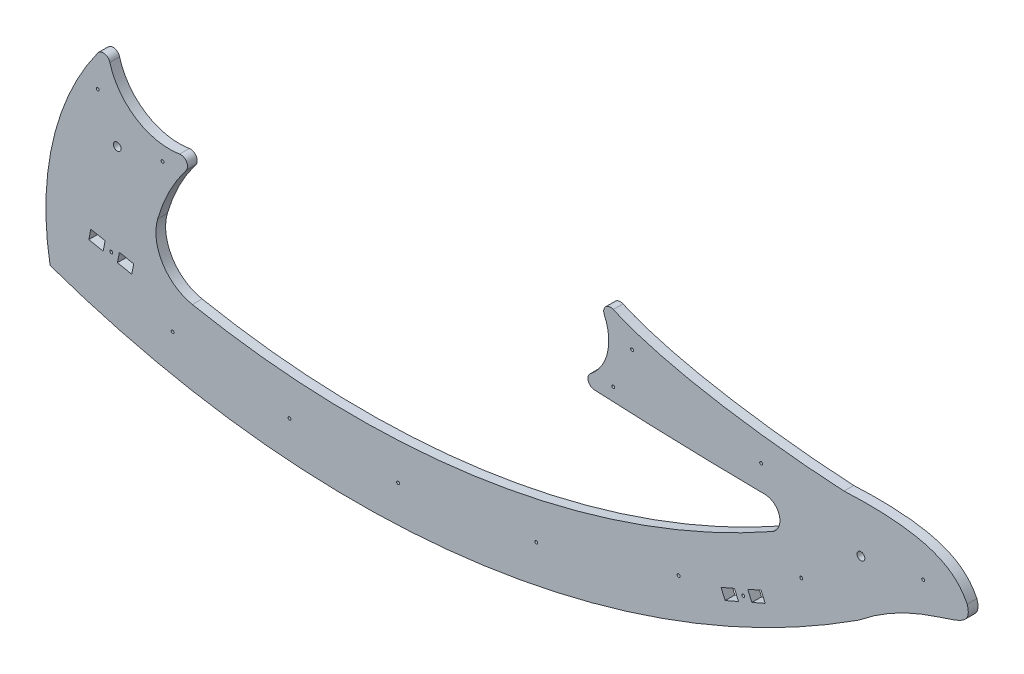
SolidWorks part; units mm, degrees
material "Teak"
ref_plane "Front Plane" through (0, 0, 0) normal (0, 0, 1) x (1, 0, 0)
ref_plane "Top Plane" through (0, 0, 0) normal (0, 1, 0) x (1, 0, 0)
ref_plane "Right Plane" through (0, 0, 0) normal (1, 0, 0) x (0, 0, -1)
sketch "Несущая боковая" plane through (0, 0, 0) normal (0, 0, 1) x (1, 0, 0)
  line L6 (398.785, -200.6515) -> (-79.2948, -202.7)
  arc A0 (568.0858, 187.1743) -> (604.9253, 231.748) centre (555.0835, 235.431) ccw
  arc A1 (604.9253, 231.748) -> (587.3016, 257.9076) centre (579.4885, 233.6276) ccw
  arc A2 (587.3016, 257.9076) -> (556.344, 256.9224) centre (573.2016, 214.0906) ccw
  arc A4 (-130.7033, -495.9282) -> (-177.7889, -420.4808) centre (-169.1009, -467.4752) ccw
  arc A7 (-130.7033, -495.9282) -> (-181.6944, -712.4375) centre (95.3308, -663.4217) ccw
  arc A8 (-183.8786, -325.353) -> (-177.7889, -420.4808) centre (-186.515, -373.2806) ccw
  arc A9 (-112.9747, -345.6094) -> (-183.8786, -325.353) centre (-193.0224, -491.581) ccw
  arc A11 (23.5507, -511.1423) -> (553.7515, -548.6326) centre (601.0308, 3887.8918) ccw
  arc A12 (7.2112, -514.4863) -> (-70.9864, -615.6156) centre (95.3308, -663.4217) ccw
  arc A13 (-70.9864, -615.6156) -> (-35.2447, -674.0637) centre (-26.3207, -628.4543) ccw
  arc A14 (23.5507, -511.1423) -> (7.2112, -514.4863) centre (20.2245, -536.4807) ccw
  arc A15 (-181.6944, -712.4375) -> (650.1904, -612.5982) centre (132.6498, 184.0228) ccw
  arc A16 (-35.2447, -674.0637) -> (561.2917, -578.0579) centre (132.6498, 184.0228) ccw
  arc A17 (561.2917, -578.0579) -> (553.7515, -548.6326) centre (553.584, -564.3543) ccw
  spline S0 degree 3 poles (556.344, 256.9224) (413.4931, 200.7) (492.8039, -30.4464) (410.7267, -175.5993) knots 0.000401 0.000401 0.000401 0.000401 0.043478 0.043478 0.043478 0.043478
  spline S1 degree 3 poles (410.7267, -175.5993) (407.231, -184.6492) (403.2193, -192.9282) (398.785, -200.6515) knots 0.043478 0.043478 0.043478 0.043478 0.086957 0.086957 0.086957 0.086957
  spline S2 degree 3 poles (-79.2948, -202.7) (-78.5172, -227.7) (-66.7741, -249.7094) (-44.1772, -268.7587) knots 0.130435 0.130435 0.130435 0.130435 0.173913 0.173913 0.173913 0.173913
  spline S3 degree 3 poles (-44.1772, -268.7587) (-12.7058, -245.829) (38.9597, -231.7344) (82.6666, -241.804) knots 0.173913 0.173913 0.173913 0.173913 0.217391 0.217391 0.217391 0.217391
  spline S4 degree 3 poles (82.6666, -241.804) (105.6787, -251.6525) (111.2464, -268.6919) (94.2115, -290.7234) knots 0.217391 0.217391 0.217391 0.217391 0.26087 0.26087 0.26087 0.26087
  spline S5 degree 3 poles (94.2115, -290.7234) (87.1581, -299.8457) (74.9831, -308.4217) (61.0599, -320.5021) knots 0.26087 0.26087 0.26087 0.26087 0.304348 0.304348 0.304348 0.304348
  spline S6 degree 3 poles (61.0599, -320.5021) (47.3806, -331.8412) (34.8832, -345.2678) (22.8705, -359.1067) knots 0.304348 0.304348 0.304348 0.304348 0.347826 0.347826 0.347826 0.347826
  spline S7 degree 3 poles (22.8705, -359.1067) (-5.5844, -391.8897) (-25.5922, -386.6363) (-46.4172, -376.7876) knots 0.347826 0.347826 0.347826 0.347826 0.391304 0.391304 0.391304 0.391304
  spline S8 degree 3 poles (-46.4172, -376.7876) (-71.9902, -366.2219) (-92.784, -356.6815) (-112.9747, -345.6094) knots 0.391304 0.391304 0.391304 0.391304 0.434783 0.434783 0.434783 0.434783
  spline S15 degree 3 poles (650.1904, -612.5982) (721.7263, -555.1366) (771.3742, -572.8028) (761.971, -542.4383) knots 0.695652 0.695652 0.695652 0.695652 0.73913 0.73913 0.73913 0.73913
  spline S16 degree 3 poles (761.971, -542.4383) (749.9881, -518.2511) (723.1034, -500.8362) (635.2399, -505.0064) knots 0.73913 0.73913 0.73913 0.73913 0.782609 0.782609 0.782609 0.782609
  spline S17 degree 3 poles (635.2399, -505.0064) (572.992, -501.9328) (433.5503, -486.7788) (380.9104, -452.9037) knots 0.782609 0.782609 0.782609 0.782609 0.826087 0.826087 0.826087 0.826087
  spline S18 degree 3 poles (380.9104, -452.9037) (364.7659, -442.5143) (356.7862, -430.3638) (361.7026, -416.2609) knots 0.826087 0.826087 0.826087 0.826087 0.869565 0.869565 0.869565 0.869565
  spline S19 degree 3 poles (361.7026, -416.2609) (369.7577, -319.5618) (455.7474, -287.137) (480.2427, -200.3025) knots 0.869565 0.869565 0.869565 0.869565 0.913043 0.913043 0.913043 0.913043
  spline S20 degree 3 poles (480.2427, -200.3025) (553.5443, -5.6015) (495.01, 115.2768) (568.0858, 187.1743) knots 0.913043 0.913043 0.913043 0.913043 0.956522 0.956522 0.956522 0.956522
  spline S31 degree 3 poles (97.4618, -368.9486) (168.6207, -296.3511) (255.442, -250.0892) (374.5085, -234.3308) knots 0.75 0.75 0.75 0.75 1 1 1 1
  spline S32 degree 3 poles (92.0908, -427.5464) (69.7947, -412.5311) (70.4905, -396.4567) (97.4618, -368.9486) knots 0.5 0.5 0.5 0.5 0.75 0.75 0.75 0.75
  spline S33 degree 3 poles (247.8827, -396.6458) (222.4754, -441.0979) (152.6914, -451.7196) (92.0908, -427.5464) knots 0.25 0.25 0.25 0.25 0.5 0.5 0.5 0.5
  spline S34 degree 3 poles (374.5085, -234.3308) (336.7044, -278.0035) (285.6362, -310.9643) (247.8827, -396.6458) knots 0 0 0 0 0.25 0.25 0.25 0.25
  dimension "D2" = 48
sketch "Боковая под поперечины" plane through (0, 0, 0) normal (0, 0, 1) x (1, 0, 0)
  line L15 (-159.6049, -346.9107) -> (-207.6507, -344.8161) construction
  line L16 (-207.6507, -344.8161) -> (-218.5759, -409.003)
  line L56 (-207.6507, -344.8161) -> (-159.6963, -346.9068)
  line L57 (-159.6963, -346.9068) -> (-148.2015, -350.3521)
  line L58 (-148.2015, -350.3521) -> (-104.2437, -369.6319)
  line L59 (-104.2437, -369.6319) -> (-95.353, -374.2095)
  line L60 (-95.353, -374.2095) -> (-51.5894, -393.9261)
  line L61 (-51.5894, -393.9261) -> (-42.3459, -397.7417)
  line L62 (-42.3459, -397.7417) -> (2.1537, -415.7357)
  line L63 (2.1537, -415.7357) -> (11.4455, -419.432)
  line L64 (11.4455, -419.432) -> (56.3986, -436.2612)
  line L65 (56.3986, -436.2612) -> (65.8381, -439.5619)
  line L66 (65.8381, -439.5619) -> (111.7403, -453.5971)
  line L67 (111.7403, -453.5971) -> (121.3499, -456.3643)
  line L68 (121.3499, -456.3643) -> (169.2689, -459.1514)
  line L69 (169.2689, -459.1514) -> (179.2066, -458.0374)
  line L70 (179.2066, -458.0374) -> (224.5179, -442.198)
  line L71 (224.5179, -442.198) -> (232.8956, -436.7378)
  line L72 (232.8956, -436.7378) -> (261.7321, -398.3651)
  line L73 (261.7321, -398.3651) -> (267.2053, -389.9959)
  line L74 (267.2053, -389.9959) -> (294.9373, -350.8177)
  line L75 (294.9373, -350.8177) -> (300.8954, -342.7864)
  line L76 (300.8954, -342.7864) -> (330.585, -305.0699)
  line L77 (330.585, -305.0699) -> (336.9867, -297.3877)
  line L78 (336.9867, -297.3877) -> (368.9263, -261.5566)
  line L79 (368.9263, -261.5566) -> (376.1332, -254.6241)
  line L80 (376.1332, -254.6241) -> (406.9239, -217.801)
  line L81 (406.9239, -217.801) -> (412.4436, -209.4624)
  line L82 (412.4436, -209.4624) -> (434.4129, -166.7851)
  line L83 (438.0837, -157.4832) -> (452.6073, -111.7332)
  line L84 (452.6073, -111.7332) -> (454.9033, -102.0003)
  line L85 (454.9033, -102.0003) -> (464.25, -54.9191)
  line L86 (464.25, -54.9191) -> (465.6878, -45.023)
  line L87 (465.6878, -45.023) -> (472.014, 2.5582)
  line L88 (472.014, 2.5582) -> (473.0512, 12.5043)
  line L89 (473.0512, 12.5043) -> (478.3742, 60.2082)
  line L90 (478.3742, 60.2082) -> (479.4656, 70.1485)
  line L91 (479.4656, 70.1485) -> (486.2184, 117.6711)
  line L92 (486.2184, 117.6711) -> (487.9962, 127.5118)
  line L93 (487.9962, 127.5118) -> (500.2801, 173.9134)
  line L94 (500.2801, 173.9134) -> (504.8877, 188.1882)
  line L95 (504.8877, 188.1882) -> (532.6089, 227.3741)
  line L96 (532.6089, 227.3741) -> (546.1164, 235.9502)
  line L97 (546.1164, 235.9502) -> (589.1375, 257.2382)
  line L99 (434.4129, -166.7851) -> (438.0837, -157.4832)
  arc A4 (568.0858, 187.1743) -> (604.9253, 231.748) centre (554.9668, 235.5274) ccw
  arc A7 (604.9253, 231.748) -> (589.1375, 257.2382) centre (579.4223, 233.5866) ccw
  arc A10 (604.9253, 231.748) -> (587.3016, 257.9076) centre (579.4885, 233.6276) ccw construction
  arc A11 (-121.8206, -474.4411) -> (-17.3364, -532.0713) centre (-58.8058, -483.7252) ccw
  arc A12 (7.2112, -514.4863) -> (-17.3364, -532.0713) centre (95.3308, -663.4217) ccw
  arc A13 (23.5507, -511.1423) -> (7.2112, -514.4863) centre (20.2245, -536.4807) ccw
  arc A15 (-121.8206, -474.4411) -> (-177.7889, -420.4808) centre (-169.1009, -467.4752) ccw
  arc A16 (23.5507, -511.1423) -> (341.0431, -541.2606) centre (601.0308, 3887.8918) ccw
  arc A17 (-130.7033, -495.9282) -> (-177.7889, -420.4808) centre (-169.1009, -467.4752) ccw construction
  arc A18 (-183.8786, -325.353) -> (-177.7889, -420.4808) centre (-186.515, -373.2806) ccw construction
  arc A19 (-218.5759, -409.003) -> (-177.7889, -420.4808) centre (-186.515, -373.2806) ccw
  arc A20 (23.5507, -511.1423) -> (553.7515, -548.6326) centre (601.0308, 3887.8918) ccw construction
  arc A21 (23.5507, -511.1423) -> (7.2112, -514.4863) centre (20.2245, -536.4807) ccw construction
  arc A22 (7.2112, -514.4863) -> (-70.9864, -615.6156) centre (95.3308, -663.4217) ccw construction
  arc A23 (341.0431, -541.2606) -> (375.7523, -454.4299) centre (343.931, -492.0624) ccw
  spline S13 degree 3 poles (375.7523, -454.4299) (361.34, -442.2431) (355.1113, -429.3811) (361.7026, -416.2609) knots 0.5 0.5 0.5 0.5 0.533333 0.533333 0.533333 0.533333
  spline S14 degree 3 poles (361.7026, -416.2609) (369.7577, -319.5618) (455.7474, -287.137) (480.2427, -200.3025) knots 0.533333 0.533333 0.533333 0.533333 0.566667 0.566667 0.566667 0.566667
  spline S15 degree 3 poles (480.2427, -200.3025) (553.5444, -5.6014) (495.0101, 115.2768) (568.0858, 187.1743) knots 0.566667 0.566667 0.566667 0.566667 0.6 0.6 0.6 0.6
  point P66 (608.2751, 264.1653)
  point P67 (553.7309, 240.2756)
  point P74 (-221.3236, -344.22)
  dimension "D1" = 48
  dimension "D2" = 12
  dimension "D3" = 10
  dimension "D10" = 16
  dimension "D11" = 15
extrude "Несущая" add sketch "Несущая боковая" along normal blind 10
extrude "Боковая" [suppressed] add sketch "Боковая под поперечины" along normal blind 10
sketch "Sketch3" [suppressed] plane through (0, 0, 0) normal (0, 0, 1) x (1, 0, 0)
  line L0 (546.1164, 235.9502) -> (589.1375, 257.2382) construction
  line L2 (-206.3501, -396.7709) -> (-202.6586, -375.0829)
  line L3 (-216.2083, -395.093) -> (-212.5168, -373.4049)
  line L6 (-216.2083, -395.093) -> (-206.3501, -396.7709)
  line L10 (-207.6507, -344.8161) -> (-194.6631, -345.3823) construction
  line L11 (-207.6507, -344.8161) -> (-208.0863, -354.8066) construction
  line L12 (-159.6963, -346.9068) -> (-160.1319, -356.8973) construction
  line L13 (-208.0863, -354.8066) -> (-195.0986, -355.3728) construction
  line L14 (-194.6631, -345.3823) -> (-195.0986, -355.3728)
  line L15 (-172.684, -346.3405) -> (-173.1195, -356.331)
  line L16 (-173.1195, -356.331) -> (-160.1319, -356.8973) construction
  line L17 (-195.0986, -355.3728) -> (-173.1195, -356.331)
  line L18 (-172.684, -346.3405) -> (-159.6963, -346.9068) construction
  line L19 (-194.6631, -345.3823) -> (-172.684, -346.3405)
  line L37 (-136.2963, -355.5737) -> (-140.3129, -364.7316)
  line L38 (-116.149, -364.4103) -> (-120.1656, -373.5681)
  line L40 (-152.2182, -359.51) -> (-140.3129, -364.7316) construction
  line L41 (-116.149, -364.4103) -> (-104.2437, -369.6319) construction
  line L42 (-140.3129, -364.7316) -> (-120.1656, -373.5681)
  line L43 (-104.2437, -369.6319) -> (-108.2603, -378.7897) construction
  line L44 (-120.1656, -373.5681) -> (-108.2603, -378.7897) construction
  line L45 (-148.2015, -350.3521) -> (-136.2963, -355.5737) construction
  line L46 (-136.2963, -355.5737) -> (-116.149, -364.4103)
  line L47 (-148.2015, -350.3521) -> (-152.2182, -359.51) construction
  line L48 (-104.2437, -369.6319) -> (-148.2015, -350.3521) construction
  line L49 (-63.442, -388.5862) -> (-67.5496, -397.7036)
  line L50 (-83.5003, -379.5494) -> (-63.442, -388.5862)
  line L51 (-83.5003, -379.5494) -> (-87.608, -388.6668)
  line L52 (-63.442, -388.5862) -> (-51.5894, -393.9261) construction
  line L53 (-99.4606, -383.3269) -> (-87.608, -388.6668) construction
  line L54 (-51.5894, -393.9261) -> (-55.697, -403.0436) construction
  line L55 (-95.353, -374.2095) -> (-83.5003, -379.5494) construction
  line L56 (-87.608, -388.6668) -> (-67.5496, -397.7036)
  line L57 (-67.5496, -397.7036) -> (-55.697, -403.0436) construction
  line L58 (-95.353, -374.2095) -> (-99.4606, -383.3269) construction
  line L59 (-34.0427, -411.8858) -> (-13.647, -420.1331)
  line L60 (-30.2939, -402.615) -> (-9.8983, -410.8623)
  line L61 (-42.3459, -397.7417) -> (-30.2939, -402.615) construction
  line L62 (-9.8983, -410.8623) -> (2.1537, -415.7357) construction
  line L63 (-46.0946, -407.0124) -> (-34.0427, -411.8858) construction
  line L64 (-9.8983, -410.8623) -> (-13.647, -420.1331)
  line L65 (-42.3459, -397.7417) -> (-46.0946, -407.0124) construction
  line L66 (-13.647, -420.1331) -> (-1.595, -425.0064) construction
  line L67 (-30.2939, -402.615) -> (-34.0427, -411.8858)
  line L68 (2.1537, -415.7357) -> (-1.595, -425.0064) construction
  line L69 (44.2238, -431.7033) -> (40.7177, -441.0685)
  line L70 (56.3986, -436.2612) -> (52.8925, -445.6264) construction
  line L71 (23.6203, -423.9899) -> (44.2238, -431.7033)
  line L72 (23.6203, -423.9899) -> (20.1142, -433.3551)
  line L73 (7.9394, -428.7972) -> (20.1142, -433.3551) construction
  line L74 (11.4455, -419.432) -> (23.6203, -423.9899) construction
  line L75 (44.2238, -431.7033) -> (56.3986, -436.2612) construction
  line L76 (11.4455, -419.432) -> (7.9394, -428.7972) construction
  line L77 (40.7177, -441.0685) -> (52.8925, -445.6264) construction
  line L78 (20.1142, -433.3551) -> (40.7177, -441.0685)
  line L79 (96.3845, -459.3589) -> (108.8163, -463.1601) construction
  line L80 (65.8381, -439.5619) -> (62.9141, -449.1249) construction
  line L81 (99.3085, -449.7959) -> (96.3845, -459.3589)
  line L82 (78.27, -443.3631) -> (75.346, -452.9261)
  line L83 (65.8381, -439.5619) -> (78.27, -443.3631) construction
  line L84 (62.9141, -449.1249) -> (75.346, -452.9261) construction
  line L85 (99.3085, -449.7959) -> (111.7403, -453.5971) construction
  line L86 (111.7403, -453.5971) -> (108.8163, -463.1601) construction
  line L87 (75.346, -452.9261) -> (96.3845, -459.3589)
  line L88 (78.27, -443.3631) -> (99.3085, -449.7959)
  line L89 (120.7692, -466.3474) -> (133.7473, -467.1023) construction
  line L90 (156.2908, -458.3965) -> (169.2689, -459.1514) construction
  line L91 (133.7473, -467.1023) -> (155.7102, -468.3797)
  line L92 (156.2908, -458.3965) -> (155.7102, -468.3797)
  line L93 (155.7102, -468.3797) -> (168.6882, -469.1345) construction
  line L94 (121.3499, -456.3643) -> (134.3279, -457.1191) construction
  line L95 (134.3279, -457.1191) -> (156.2908, -458.3965)
  line L96 (121.3499, -456.3643) -> (120.7692, -466.3474) construction
  line L97 (134.3279, -457.1191) -> (133.7473, -467.1023)
  line L98 (169.2689, -459.1514) -> (168.6882, -469.1345) construction
  line L99 (215.546, -455.9277) -> (227.8178, -451.6378) construction
  line L100 (191.4784, -453.7475) -> (212.2461, -446.4878)
  line L101 (191.4784, -453.7475) -> (194.7783, -463.1874)
  line L102 (182.5065, -467.4772) -> (194.7783, -463.1874) construction
  line L103 (224.5179, -442.198) -> (227.8178, -451.6378) construction
  line L104 (194.7783, -463.1874) -> (215.546, -455.9277)
  line L105 (179.2066, -458.0374) -> (182.5065, -467.4772) construction
  line L106 (212.2461, -446.4878) -> (224.5179, -442.198) construction
  line L107 (179.2066, -458.0374) -> (191.4784, -453.7475) construction
  line L108 (212.2461, -446.4878) -> (215.546, -455.9277)
  line L109 (248.6998, -432.3528) -> (261.9165, -414.7653)
  line L110 (261.9165, -414.7653) -> (269.7264, -404.3728) construction
  line L111 (240.8899, -442.7454) -> (248.6998, -432.3528) construction
  line L112 (240.7055, -426.3452) -> (248.6998, -432.3528)
  line L113 (253.9222, -408.7577) -> (261.7321, -398.3651) construction
  line L114 (261.7321, -398.3651) -> (269.7264, -404.3728) construction
  line L115 (232.8956, -436.7378) -> (240.7055, -426.3452) construction
  line L116 (240.7055, -426.3452) -> (253.9222, -408.7577)
  line L117 (232.8956, -436.7378) -> (240.8899, -442.7454) construction
  line L118 (253.9222, -408.7577) -> (261.9165, -414.7653)
  line L119 (267.2053, -389.9959) -> (274.7161, -379.3851) construction
  line L120 (267.2053, -389.9959) -> (275.3674, -395.7734) construction
  line L121 (275.3674, -395.7734) -> (282.8782, -385.1626) construction
  line L122 (274.7161, -379.3851) -> (282.8782, -385.1626)
  line L123 (282.8782, -385.1626) -> (295.5887, -367.2059)
  line L124 (287.4266, -361.4284) -> (295.5887, -367.2059)
  line L125 (294.9373, -350.8177) -> (303.0995, -356.5952) construction
  line L126 (295.5887, -367.2059) -> (303.0995, -356.5952) construction
  line L127 (287.4266, -361.4284) -> (294.9373, -350.8177) construction
  line L128 (274.7161, -379.3851) -> (287.4266, -361.4284)
  line L129 (330.4016, -321.4701) -> (338.4426, -311.2553) construction
  line L130 (316.7939, -338.7569) -> (330.4016, -321.4701)
  line L131 (308.9363, -332.5715) -> (322.5441, -315.2848)
  line L132 (300.8954, -342.7864) -> (308.9363, -332.5715) construction
  line L133 (300.8954, -342.7864) -> (308.753, -348.9717) construction
  line L134 (308.9363, -332.5715) -> (316.7939, -338.7569)
  line L135 (322.5441, -315.2848) -> (330.4016, -321.4701)
  line L136 (308.753, -348.9717) -> (316.7939, -338.7569) construction
  line L137 (330.585, -305.0699) -> (338.4426, -311.2553) construction
  line L138 (322.5441, -315.2848) -> (330.585, -305.0699) construction
  line L139 (336.9867, -297.3877) -> (344.4515, -304.0418) construction
  line L140 (360.276, -271.2609) -> (367.7408, -277.915)
  line L141 (367.7408, -277.915) -> (376.3911, -268.2107) construction
  line L142 (344.4515, -304.0418) -> (353.1018, -294.3375) construction
  line L143 (353.1018, -294.3375) -> (367.7408, -277.915)
  line L144 (336.9867, -297.3877) -> (345.637, -287.6834) construction
  line L145 (368.9263, -261.5566) -> (376.3911, -268.2107) construction
  line L146 (360.276, -271.2609) -> (368.9263, -261.5566) construction
  line L147 (345.637, -287.6834) -> (360.276, -271.2609)
  line L148 (345.637, -287.6834) -> (353.1018, -294.3375)
  line L149 (406.2562, -234.1886) -> (414.5953, -224.2157) construction
  line L150 (398.5847, -227.7739) -> (406.2562, -234.1886)
  line L151 (392.1438, -251.0659) -> (406.2562, -234.1886)
  line L152 (383.8047, -261.0388) -> (392.1438, -251.0659) construction
  line L153 (406.9239, -217.801) -> (414.5953, -224.2157) construction
  line L154 (376.1332, -254.6241) -> (384.4724, -244.6512) construction
  line L155 (376.1332, -254.6241) -> (383.8047, -261.0388) construction
  line L156 (398.5847, -227.7739) -> (406.9239, -217.801) construction
  line L157 (384.4724, -244.6512) -> (392.1438, -251.0659)
  line L158 (384.4724, -244.6512) -> (398.5847, -227.7739)
  line L159 (437.354, -182.9205) -> (443.304, -171.3621) construction
  line L160 (428.4629, -178.3436) -> (434.4129, -166.7851) construction
  line L161 (428.4629, -178.3436) -> (437.354, -182.9205)
  line L162 (418.3936, -197.904) -> (427.2847, -202.4809)
  line L163 (427.2847, -202.4809) -> (437.354, -182.9205)
  line L164 (412.4436, -209.4624) -> (421.3346, -214.0393) construction
  line L165 (421.3346, -214.0393) -> (427.2847, -202.4809) construction
  line L166 (434.4129, -166.7851) -> (443.304, -171.3621) construction
  line L167 (418.3936, -197.904) -> (428.4629, -178.3436)
  line L168 (412.4436, -209.4624) -> (418.3936, -197.904) construction
  line L169 (447.6149, -160.509) -> (451.5484, -148.1183) construction
  line L170 (448.6738, -124.1238) -> (452.6073, -111.7332) construction
  line L171 (442.0172, -145.0926) -> (451.5484, -148.1183)
  line L172 (448.6738, -124.1238) -> (458.205, -127.1496)
  line L173 (438.0837, -157.4832) -> (442.0172, -145.0926) construction
  line L174 (458.205, -127.1496) -> (462.1385, -114.7589) construction
  line L175 (442.0172, -145.0926) -> (448.6738, -124.1238)
  line L176 (452.6073, -111.7332) -> (462.1385, -114.7589) construction
  line L177 (438.0837, -157.4832) -> (447.6149, -160.509) construction
  line L178 (451.5484, -148.1183) -> (458.205, -127.1496)
  line L179 (-51.5894, -393.9261) -> (-95.353, -374.2095) construction
  line L180 (2.1537, -415.7357) -> (-42.3459, -397.7417) construction
  line L181 (56.3986, -436.2612) -> (11.4455, -419.432) construction
  line L182 (368.9263, -261.5566) -> (336.9867, -297.3877) construction
  line L183 (406.9239, -217.801) -> (376.1332, -254.6241) construction
  line L184 (434.4129, -166.7851) -> (412.4436, -209.4624) construction
  line L185 (452.6073, -111.7332) -> (438.0837, -157.4832) construction
  line L186 (464.7118, -103.9476) -> (467.2432, -91.1964) construction
  line L187 (457.4347, -89.2492) -> (461.7186, -67.6703)
  line L188 (454.9033, -102.0003) -> (457.4347, -89.2492) construction
  line L189 (457.4347, -89.2492) -> (467.2432, -91.1964)
  line L190 (461.7186, -67.6703) -> (464.25, -54.9191) construction
  line L191 (454.9033, -102.0003) -> (464.7118, -103.9476) construction
  line L192 (464.25, -54.9191) -> (474.0586, -56.8664) construction
  line L193 (467.2432, -91.1964) -> (471.5272, -69.6175)
  line L194 (461.7186, -67.6703) -> (471.5272, -69.6175)
  line L195 (471.5272, -69.6175) -> (474.0586, -56.8664) construction
  line L196 (467.4011, -32.1364) -> (470.3006, -10.3284)
  line L197 (465.6878, -45.023) -> (467.4011, -32.1364) construction
  line L198 (472.014, 2.5582) -> (481.9268, 1.2403) construction
  line L199 (477.3139, -33.4544) -> (480.2134, -11.6463)
  line L200 (470.3006, -10.3284) -> (472.014, 2.5582) construction
  line L201 (480.2134, -11.6463) -> (481.9268, 1.2403) construction
  line L202 (465.6878, -45.023) -> (475.6006, -46.341) construction
  line L203 (467.4011, -32.1364) -> (477.3139, -33.4544)
  line L204 (470.3006, -10.3284) -> (480.2134, -11.6463)
  line L205 (475.6006, -46.341) -> (477.3139, -33.4544) construction
  line L206 (473.0512, 12.5043) -> (474.4928, 25.4241) construction
  line L207 (474.4928, 25.4241) -> (476.9325, 47.2884)
  line L208 (473.0512, 12.5043) -> (482.9895, 11.3953) construction
  line L209 (486.8708, 46.1795) -> (488.3125, 59.0993) construction
  line L210 (476.9325, 47.2884) -> (486.8708, 46.1795)
  line L211 (474.4928, 25.4241) -> (484.4311, 24.3152)
  line L212 (482.9895, 11.3953) -> (484.4311, 24.3152) construction
  line L213 (484.4311, 24.3152) -> (486.8708, 46.1795)
  line L214 (478.3742, 60.2082) -> (488.3125, 59.0993) construction
  line L215 (476.9325, 47.2884) -> (478.3742, 60.2082) construction
  line L216 (486.2184, 117.6711) -> (496.119, 116.2643) construction
  line L217 (481.2945, 83.0192) -> (484.3895, 104.8004)
  line L218 (491.195, 81.6124) -> (494.2901, 103.3936)
  line L219 (494.2901, 103.3936) -> (496.119, 116.2643) construction
  line L220 (484.3895, 104.8004) -> (486.2184, 117.6711) construction
  line L221 (484.3895, 104.8004) -> (494.2901, 103.3936)
  line L222 (479.4656, 70.1485) -> (481.2945, 83.0192) construction
  line L223 (479.4656, 70.1485) -> (489.3661, 68.7417) construction
  line L224 (481.2945, 83.0192) -> (491.195, 81.6124)
  line L225 (489.3661, 68.7417) -> (491.195, 81.6124) construction
  line L226 (500.2801, 173.9134) -> (509.9471, 171.3543) construction
  line L227 (497.6632, 124.9527) -> (500.9901, 137.5198) construction
  line L228 (491.3231, 140.0789) -> (496.9532, 161.3463)
  line L229 (506.6202, 158.7872) -> (509.9471, 171.3543) construction
  line L230 (487.9962, 127.5118) -> (491.3231, 140.0789) construction
  line L231 (487.9962, 127.5118) -> (497.6632, 124.9527) construction
  line L232 (491.3231, 140.0789) -> (500.9901, 137.5198)
  line L233 (496.9532, 161.3463) -> (506.6202, 158.7872)
  line L234 (500.9901, 137.5198) -> (506.6202, 158.7872)
  line L235 (496.9532, 161.3463) -> (500.2801, 173.9134) construction
  line L236 (512.3955, 198.8011) -> (525.1011, 216.7613)
  line L237 (504.8877, 188.1882) -> (513.0514, 182.413) construction
  line L238 (525.1011, 216.7613) -> (532.6089, 227.3741) construction
  line L239 (512.3955, 198.8011) -> (520.5593, 193.0258)
  line L240 (525.1011, 216.7613) -> (533.2648, 210.986)
  line L241 (532.6089, 227.3741) -> (540.7726, 221.5989) construction
  line L242 (504.8877, 188.1882) -> (512.3955, 198.8011) construction
  line L243 (533.2648, 210.986) -> (540.7726, 221.5989) construction
  line L244 (513.0514, 182.413) -> (520.5593, 193.0258) construction
  line L245 (520.5593, 193.0258) -> (533.2648, 210.986)
  line L246 (589.1375, 257.2382) -> (593.5725, 248.2755) construction
  line L247 (557.7679, 241.7157) -> (562.2029, 232.7529)
  line L248 (546.1164, 235.9502) -> (557.7679, 241.7157) construction
  line L249 (577.4859, 251.4727) -> (581.9209, 242.51)
  line L250 (581.9209, 242.51) -> (593.5725, 248.2755) construction
  line L251 (557.7679, 241.7157) -> (577.4859, 251.4727)
  line L252 (546.1164, 235.9502) -> (550.5514, 226.9874) construction
  line L253 (562.2029, 232.7529) -> (581.9209, 242.51)
  line L254 (577.4859, 251.4727) -> (589.1375, 257.2382) construction
  line L255 (550.5514, 226.9874) -> (562.2029, 232.7529) construction
  line L256 (464.25, -54.9191) -> (454.9033, -102.0003) construction
  line L257 (472.014, 2.5582) -> (465.6878, -45.023) construction
  line L258 (486.2184, 117.6711) -> (479.4656, 70.1485) construction
  line L259 (500.2801, 173.9134) -> (487.9962, 127.5118) construction
  line L260 (487.9962, 127.5118) -> (486.2184, 117.6711) construction
  line L261 (532.6089, 227.3741) -> (504.8877, 188.1882) construction
  line L262 (504.8877, 188.1882) -> (500.2801, 173.9134) construction
  line L264 (-212.5168, -373.4049) -> (-202.6586, -375.0829)
  line L269 (-207.6507, -344.8161) -> (-218.5759, -409.003) construction
  point P1 (-214.3626, -384.2489)
  dimension "D1" = 40
  dimension "D2" = 10
  dimension "D3" = 22
extrude "Шипы" [suppressed] cut sketch "Sketch3" along normal through all
sketch "Sketch4" [suppressed] plane through (0, 0, 10) normal (0, 0, 1) x (1, 0, 0)
  line L0 (-208.4348, -362.799) -> (-221.0097, -388.653) construction
  line L1 (-221.0097, -388.653) -> (-207.6507, -344.8161) construction
  line L2 (-207.6507, -344.8161) -> (-208.4348, -362.799) construction
  line L4 (-217.7838, -439.8154) -> (-237.4507, -429.7729) construction
  line L5 (-237.4507, -429.7729) -> (-240.164, -452.0896) construction
  line L6 (-240.164, -452.0896) -> (-201.8347, -418.7702) construction
  arc A1 (-218.5759, -409.003) -> (-177.7889, -420.4808) centre (-186.515, -373.2806) ccw construction
extrude "Излишки" [suppressed] cut sketch "Sketch4" against normal up to next
sketch "Sketch5" plane through (0, 0, 10) normal (0, 0, 1) x (1, 0, 0)
  line L1 (40.6613, -192.1859) -> (90.6608, -191.9717)
  line L2 (40.6613, -192.1859) -> (40.7041, -202.1858)
  line L3 (40.7041, -202.1858) -> (90.7037, -201.9716)
  line L4 (90.6608, -191.9717) -> (90.7037, -201.9716)
  line L5 (398.785, -200.6515) -> (-79.2948, -202.7) construction
  line L6 (240.6594, -191.329) -> (290.659, -191.1147)
  line L7 (240.6594, -191.329) -> (240.7023, -201.3289)
  line L8 (240.7023, -201.3289) -> (290.7018, -201.1146)
  line L9 (290.659, -191.1147) -> (290.7018, -201.1146)
  dimension "D1" = 10
  dimension "D2" = 150
  dimension "D3" = 120
  dimension "D4" = 50
extrude "Шипы на подлокотниках" [suppressed] add sketch "Sketch5" against normal up to surface (10 mm away) up to face at (172.6744, -583.2036, 0)
sketch "Sketch6" plane through (0, 0, 10) normal (0, 0, 1) x (1, 0, 0)
  line L0 (-139.8462, -659.6686) -> (-141.8053, -669.4748)
  line L1 (-141.8053, -669.4748) -> (-127.0959, -672.4134)
  line L2 (-127.0959, -672.4134) -> (-125.1369, -662.6072)
  line L3 (-125.1369, -662.6072) -> (-139.8462, -659.6686)
  line L4 (-127.0959, -672.4134) -> (-112.3866, -675.352) construction
  line L5 (-112.3866, -675.352) -> (-110.4276, -665.5457)
  line L6 (-110.4276, -665.5457) -> (-95.7182, -668.4843)
  line L7 (-95.7182, -668.4843) -> (-97.6773, -678.2905)
  line L8 (-97.6773, -678.2905) -> (-112.3866, -675.352)
  line L9 (-119.7413, -673.8827) -> (-117.7822, -664.0765) construction
  line L10 (-125.1369, -662.6072) -> (-110.4276, -665.5457) construction
  line L11 (-126.1164, -667.5103) -> (-111.4071, -670.4489) construction
  line L12 (522.6672, -648.5899) -> (536.3744, -642.4979) construction
  line L13 (554.1429, -645.5439) -> (540.4358, -651.636)
  line L14 (533.5822, -654.682) -> (529.5208, -645.5439) construction
  line L15 (522.6672, -648.5899) -> (508.96, -654.682)
  line L16 (513.0214, -663.8201) -> (526.7286, -657.728)
  line L17 (526.7286, -657.728) -> (540.4358, -651.636) construction
  line L18 (526.7286, -657.728) -> (522.6672, -648.5899)
  line L19 (540.4358, -651.636) -> (536.3744, -642.4979)
  line L20 (524.6979, -653.159) -> (538.4051, -647.0669) construction
  line L21 (550.0815, -636.4058) -> (554.1429, -645.5439)
  line L22 (508.96, -654.682) -> (513.0214, -663.8201)
  line L23 (536.3744, -642.4979) -> (550.0815, -636.4058)
  circle A2 centre (531.5515, -650.113) radius 1.5
  circle A4 centre (-118.7618, -668.9796) radius 1.5
  dimension "D1" = 10
  dimension "D4" = 3
  dimension "D6" = 3
  dimension "D2" = 15
  dimension "D5" = 15
extrude "Под ребра жесткости" [suppressed] cut sketch "Sketch6" against normal up to next
sketch "Sketch7" [suppressed] plane through (0, 0, 10) normal (0, 0, 1) x (1, 0, 0)
  line L0 (567.6269, 246.5942) -> (583.0969, 215.468) construction
  line L1 (589.1375, 257.2382) -> (546.1164, 235.9502) construction
  circle A0 centre (583.0969, 215.468) radius 10 construction
  circle A1 centre (583.0969, 215.468) radius 4
  circle A2 centre (343.931, -492.0624) radius 4
  circle A3 centre (-58.8058, -483.7252) radius 4
  arc A4 (341.0431, -541.2606) -> (375.7523, -454.4299) centre (343.931, -492.0624) ccw construction
  arc A5 (-121.8206, -474.4411) -> (-17.3364, -532.0713) centre (-58.8058, -483.7252) ccw construction
  dimension "D1" = 8
  dimension "D2" = 20
extrude "Под болты М8" [suppressed] cut sketch "Sketch7" against normal blind 20
sketch "Sketch9" [suppressed] plane through (0, 0, 10) normal (0, 0, 1) x (1, 0, 0)
  circle A1 centre (-150.0179, -416.742) radius 1.5
  circle A2 centre (-19.0866, -469.5934) radius 1.5
  circle A3 centre (116.1327, -506.7832) radius 1.5
  circle A4 centre (265.4187, -506.7832) radius 1.5
  circle A5 centre (335.948, -380.5609) radius 1.5
  circle A6 centre (431.4673, -250.6533) radius 1.5
  circle A7 centre (486.9514, -124.9981) radius 1.5
  circle A8 centre (512.1042, 60.8892) radius 1.5
  dimension "D1" = 3
extrude "Под шурупы" [suppressed] cut sketch "Sketch9" against normal up to next
sketch "Sketch10" plane through (0, 0, 10) normal (0, 0, 1) x (1, 0, 0)
  line L0 (-160.015, -545.337) -> (-65.0834, -598.5055) construction
  circle A0 centre (-58.8058, -483.7252) radius 4
  circle A1 centre (343.931, -492.0624) radius 4
  circle A2 centre (583.0969, 215.468) radius 4
  circle A3 centre (-112.5492, -571.9212) radius 4
  circle A4 centre (652.6583, -554.3553) radius 4
  arc A5 (-130.7033, -495.9282) -> (-181.6944, -712.4375) centre (95.3308, -663.4217) ccw construction
  arc A6 (7.2112, -514.4863) -> (-70.9864, -615.6156) centre (95.3308, -663.4217) ccw construction
  dimension "D1" = 8
extrude "Под болты М8 в несущей" [suppressed] cut sketch "Sketch10" against normal blind 10
sketch "Sketch11" plane through (0, 0, 10) normal (0, 0, 1) x (1, 0, 0)
  line L0 (-41.7058, -557.7439) -> (378.3726, -543.294)
  line L1 (-127.0959, -672.4134) -> (-141.8053, -669.4748)
  line L2 (-132.5999, -498.5185) -> (-477.3198, -249.1207)
  line L3 (-477.3198, -249.1207) -> (641.9014, 366.4652)
  line L4 (641.9014, 366.4652) -> (806.4928, -337.8987)
  line L5 (806.4928, -337.8987) -> (445.1298, -438.4405)
  line L6 (-141.8053, -669.4748) -> (-139.7483, -659.1783)
  line L7 (-139.7483, -659.1783) -> (-125.0389, -662.1169)
  line L8 (-125.0389, -662.1169) -> (-127.0959, -672.4134)
  line L9 (-110.3296, -665.0554) -> (-95.6203, -667.994)
  line L10 (-95.6203, -667.994) -> (-97.6773, -678.2905)
  line L11 (-97.6773, -678.2905) -> (-112.3866, -675.352)
  line L12 (-112.3866, -675.352) -> (-110.3296, -665.0554)
  line L13 (-127.0959, -672.4134) -> (-112.3866, -675.352) construction
  line L14 (-110.3296, -665.0554) -> (-125.0389, -662.1169) construction
  line L15 (-117.7822, -664.0765) -> (-119.7413, -673.8827) construction
  line L16 (-126.1164, -667.5103) -> (-111.4071, -670.4489) construction
  line L17 (536.2079, -642.062) -> (549.9426, -636.0322)
  line L18 (512.9594, -663.7359) -> (508.7385, -654.1216)
  line L19 (540.4288, -651.6763) -> (536.2079, -642.062)
  line L20 (554.1634, -645.6465) -> (540.4288, -651.6763)
  line L21 (526.6941, -657.7061) -> (540.4288, -651.6763) construction
  line L22 (526.6941, -657.7061) -> (512.9594, -663.7359)
  line L23 (536.2079, -642.062) -> (522.4732, -648.0918) construction
  line L24 (529.5416, -645.5347) -> (533.5614, -654.6912) construction
  line L25 (508.7385, -654.1216) -> (522.4732, -648.0918)
  line L26 (522.4732, -648.0918) -> (526.6941, -657.7061)
  line L27 (524.6841, -653.1278) -> (538.4188, -647.0981) construction
  line L28 (549.9426, -636.0322) -> (554.1634, -645.6465)
  line L29 (237.3954, -684.0379) -> (245.8495, -759.184) construction
  arc A0 (374.3966, -530.8006) -> (388.6094, -471.2623) centre (343.931, -492.0624) ccw
  arc A1 (-120.1832, -500.7506) -> (-48.3933, -546.5634) centre (-58.8058, -483.7252) ccw
  arc A2 (-121.8206, -474.4411) -> (-17.3364, -532.0713) centre (-58.8058, -483.7252) ccw construction
  arc A3 (341.0431, -541.2606) -> (375.7523, -454.4299) centre (343.931, -492.0624) ccw construction
  arc A5 (-120.1832, -500.7506) -> (-132.5999, -498.5185) centre (-126.9285, -502.6217) ccw
  arc A6 (397.834, -461.9272) -> (388.6094, -471.2623) centre (394.9553, -468.3079) ccw
  arc A7 (374.3966, -530.8006) -> (378.3726, -543.294) centre (378.7239, -536.3028) ccw
  arc A8 (23.5507, -511.1423) -> (553.7515, -548.6326) centre (601.0308, 3887.8918) ccw construction
  arc A9 (-41.7058, -557.7439) -> (-48.3933, -546.5634) centre (-47.249, -553.4692) ccw
  arc A10 (7.2112, -514.4863) -> (-70.9864, -615.6156) centre (95.3308, -663.4217) ccw construction
  arc A11 (-130.7033, -495.9282) -> (-181.6944, -712.4375) centre (95.3308, -663.4217) ccw construction
  arc A12 (445.1298, -438.4405) -> (397.834, -461.9272) centre (482.6916, -573.4435) ccw
  circle A13 centre (-118.7618, -668.9796) radius 1.5
  circle A14 centre (-118.7618, -668.9796) radius 1.5 construction
  circle A15 centre (531.5515, -650.113) radius 1.5
  circle A16 centre (531.5515, -650.113) radius 1.5 construction
  circle A17 centre (-112.5492, -571.9212) radius 4
  circle A18 centre (652.6583, -554.3553) radius 4
  circle A19 centre (652.6583, -554.3553) radius 4 construction
  circle A20 centre (-112.5492, -571.9212) radius 4 construction
  circle A21 centre (132.6498, 184.0228) radius 912.1663 construction
  arc A22 (-181.6944, -712.4375) -> (650.1904, -612.5982) centre (132.6498, 184.0228) ccw construction
  arc A23 (-35.2447, -674.0637) -> (561.2917, -578.0579) centre (132.6498, 184.0228) ccw construction
  circle A24 centre (-55.6293, -708.5009) radius 1.5
  circle A25 centre (64.6121, -725.6026) radius 1.5
  circle A26 centre (176.3683, -727.0953) radius 1.5
  circle A27 centre (318.5821, -708.9927) radius 1.5
  circle A28 centre (465.0308, -665.4302) radius 1.5
  circle A29 centre (591.2442, -604.4813) radius 1.5
  circle A30 centre (-132.5999, -530.8006) radius 1.5
  circle A31 centre (-65.9031, -561.841) radius 1.5
  circle A32 centre (417.14, -488.0696) radius 1.5
  circle A33 centre (397.834, -530.8006) radius 1.5
  circle A34 centre (549.9426, -522.8301) radius 1.5
  circle A35 centre (716.7021, -543.294) radius 1.5
  spline S3 degree 3 poles (635.2399, -505.0064) (572.992, -501.9328) (433.5503, -486.7788) (380.9104, -452.9037) knots 0.782609 0.782609 0.782609 0.782609 0.826087 0.826087 0.826087 0.826087 construction
  point P85 (241.6225, -721.6109)
  point P115 (-65.9031, -561.841)
  point P116 (-55.6293, -708.5009)
  point P117 (0, 0)
  point P118 (318.5821, -708.5009)
  dimension "D1" = 7
  dimension "D3" = 3
  dimension "D2" = 10.5
extrude "Усиление несущей" cut sketch "Sketch11" against normal up to next
equation "\"mm\"=20"
